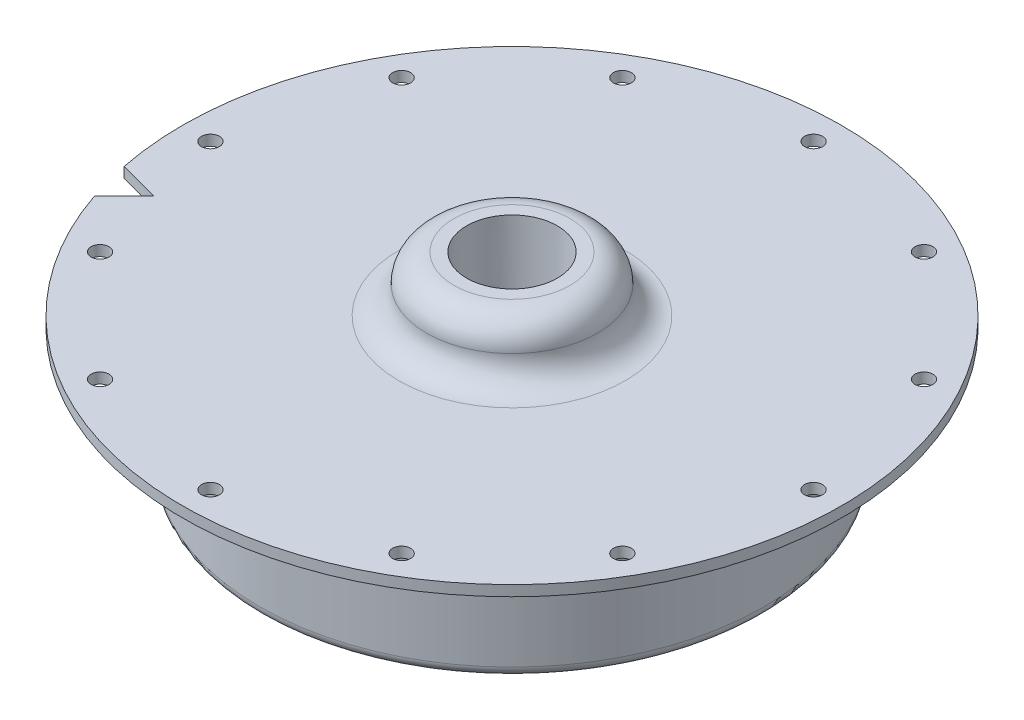
SolidWorks part; units mm, degrees
material "6063-T6"
ref_plane "Front Plane" through (0, 0, 0) normal (0, 0, 1) x (1, 0, 0)
ref_plane "Top Plane" through (0, 0, 0) normal (0, 1, 0) x (1, 0, 0)
ref_plane "Right Plane" through (0, 0, 0) normal (1, 0, 0) x (0, 0, -1)
ref_axis "Axis1" through (0, 55, 0) along (0, -1, 0)
sketch "Sketch1" plane through (0, 0, 0) normal (0, 0, 1) x (1, 0, 0)
  line L0 (-49.784, 0) -> (-39.6875, 0)
  line L1 (0, 55) -> (0, -55) construction
  line L2 (-49.784, 0) -> (-49.784, 1.5875)
  line L3 (-5.588, 9.906) -> (-8.763, 9.906)
  line L5 (-5.588, 9.906) -> (-5.588, 0)
  line L6 (-5.588, 0) -> (0, 0) construction
  line L7 (-49.784, 0) -> (-49.784, 1.5875) construction
  line L8 (-5.588, 1.5875) -> (-5.588, 0) construction
  line L9 (-38.1, -1.5875) -> (-38.1, -17.4625)
  line L11 (-34.925, -17.4625) -> (-34.925, -3.175)
  line L12 (-31.75, 0) -> (-5.588, 0)
  line L13 (0, -201000) -> (0, 249000) construction
  line L14 (-49.784, 1.5875) -> (-17.0815, 1.5875)
  arc A0 (-34.925, -3.175) -> (-31.75, 0) centre (-31.75, -3.175) cw
  arc A1 (-38.1, -1.5875) -> (-39.6875, 0) centre (-39.6875, -1.5875) ccw
  arc A2 (-17.0815, 1.5875) -> (-12.9223, 5.7467) centre (-17.0815, 5.7467) ccw
  arc A3 (-8.763, 9.906) -> (-12.9223, 5.7467) centre (-8.763, 5.7467) ccw
  arc A4 (-38.1, -17.4625) -> (-34.925, -17.4625) centre (-36.5125, -17.4625) ccw
  point P18 (-34.925, 0)
  dimension "D4" = 3.175
  dimension "D5" = 1.5875
  dimension "D1" = 3.175
  dimension "D2" = 38.1
  dimension "D3" = 17.4625
  dimension "D6" = 1.5875
  dimension "D7" = 3.175
  dimension "D8" = 9.906
revolve "Revolve1" add sketch "Sketch1" angle 360 about axis through (0, 55, 0) along (0, -1, 0)
ref_plane "Hole Location Plane" through (0, 3.175, 0) normal (0, 1, 0) x (1, 0, 0)
sketch "Hole Location" plane through (0, 3.175, 0) normal (0, 1, 0) x (1, 0, 0)
  line L0 (0, 0) -> (-45.5549, 0) construction
  circle A0 centre (0, 0) radius 45.5549 construction
  dimension "D1" = 91.1098
hole_wizard "#36 (0.1065) Diameter Hole1" positions "Sketch2" profile "Sketch3" hole size "#36" standard "ANSI Inch" end condition through all
sketch "Sketch2" plane through (0, 1.5875, 0) normal (0, 1, 0) x (1, 0, 0)
  point P0 (-45.5549, 0)
sketch "Sketch3" plane through (-45.5549, 1.5875, 0) normal (1, 0, 0) x (0, 0, 1)
  line L0 (0, 0) -> (0, 20.6375)
  line L1 (0, 20.6375) -> (1.3525, 20.6375)
  line L2 (1.3525, 20.6375) -> (1.3525, 0)
  line L5 (1.3525, 0) -> (0, 0)
  line L11 (0, -6.35) -> (0, 107.95) construction
  dimension "Thru Hole Dia." = 2.7051
  dimension "Thru Hole Depth" = 20.6375
pattern_circular "CirPattern1" count 12 over 360 of "#36 (0.1065) Diameter Hole1"
hole_wizard "1/4 NPT Tapped Hole1" positions "Sketch4" profile "Sketch5" size "1/4" standard "ANSI Inch" end condition through all
sketch "Sketch4" plane through (0, 9.906, 0) normal (0, 1, 0) x (1, 0, 0)
  point P0 (0, 0)
sketch "Sketch5" plane through (0, 9.906, 0) normal (1, 0, 0) x (0, 0, 1)
  line L0 (0, 0) -> (0, 28.956)
  line L1 (0, 28.956) -> (5.5626, 28.956)
  line L2 (-6.558, 9.906) -> (-6.8546, 0) construction
  line L3 (5.5626, 28.956) -> (5.5626, 9.906)
  line L4 (5.5626, 9.906) -> (6.558, 9.906)
  line L5 (6.558, 9.906) -> (6.8546, 0)
  line L7 (6.8546, 0) -> (0, 0)
  line L8 (0, -6.35) -> (0, 107.95) construction
  line L11 (-5.5626, 9.906) -> (-6.558, 9.906) construction
  dimension "Thru Tap Drill Dia." = 11.1252
  dimension "Thru Tap Drill Depth" = 28.956
  dimension "Thread Dia." = 13.7092
  dimension "Thread Angle" = 3.43
  dimension "Thread Depth" = 9.906
sketch "Sketch6" plane through (0, 1.5875, 0) normal (0, 1, 0) x (1, 0, 0)
  line L0 (0, 0) -> (-48.0877, -12.885) construction
  line L1 (0, 0) -> (-45.5549, 0) construction
  line L2 (-47.168, -15.9256) -> (-42.6779, -11.4355)
  line L3 (-42.6779, -11.4355) -> (-48.8115, -9.792)
  circle A0 centre (0, 0) radius 49.784 construction
  arc A1 (-47.168, -15.9256) -> (-48.8115, -9.792) centre (0, 0) cw
  circle M16 centre (0, 0) radius 49.784
  dimension "D1" = 15
  dimension "D2" = 60
  dimension "D3" = 6.35
extrude "Cut-Extrude1" cut sketch "Sketch6" against normal up to surface (1.5875 mm away) contours L2 L0 A1 | L0 L3 M16 region at (-45.9878, 1.5875, 13.4214) region at (-46.5373, 1.5875, 11.3707) up to face at (-39.4517, 0, -24.13)
equation "\"D1@Hole Location\"=\"TANK DIAMETER@Cryo Tank.Assembly\"+\"GASKET SEAT THICKNESS@Cryo Tank.Assembly\"+\"LINER THICKNESS@Cryo Tank.Assembly\"+\"SHRINK FIT DELTA@Cryo Tank.Assembly\""
equation "\"D2@Sketch1\"=\"TANK DIAMETER@Cryo Tank.Assembly\"/2"
equation "\"D3@Sketch1\"=0.5+0.125+0.0625"
